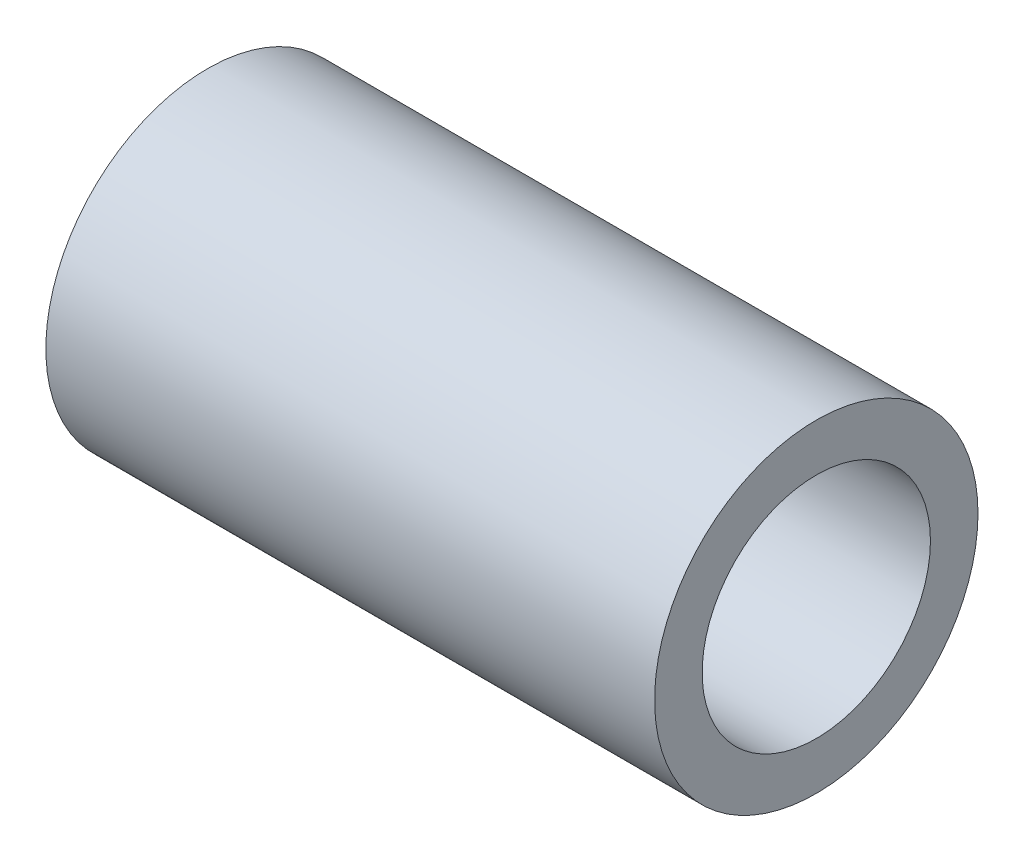
SolidWorks part; units mm, degrees
material "Silicon Rubber"
ref_plane "X-Y Datum" through (0, 0, 0) normal (0, 0, 1) x (1, 0, 0)
ref_plane "X-Z Datum" through (0, 0, 0) normal (0, 1, 0) x (1, 0, 0)
ref_plane "Y-Z Datum" through (0, 0, 0) normal (1, 0, 0) x (0, 0, -1)
sketch "Sketch1" plane through (0, 0, 0) normal (0, 0, 1) x (1, 0, 0)
  line L0 (0, 0) -> (50.8, 0)
  line L1 (55.1739, 0) -> (-55.1739, 0) construction
sweep "Sweep1" add path "Sketch1" circular profile diameter 26.9875 parameters "D3"=26.9875
sweep "Cut-Sweep1" cut path "Sketch1<3>" circular profile diameter 19.05 parameters "D3"=19.05
sketch "Sketch1<3>" plane through (0, 0, 0) normal (0, 0, 1) x (1, 0, 0) same geometry as "Sketch1"
